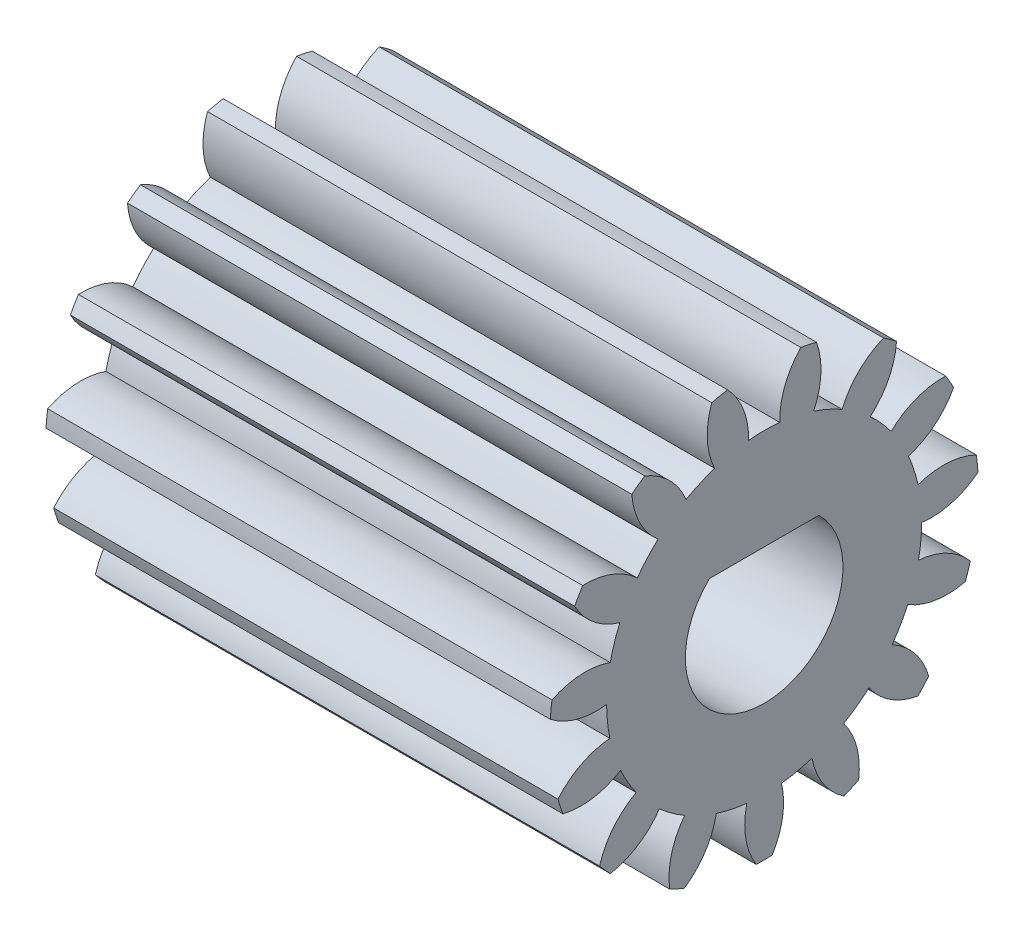
SolidWorks part; units mm, degrees
ref_plane "Plane1" through (0, 0, 0) normal (0, 0, 1) x (1, 0, 0)
ref_plane "Plane2" through (0, 0, 0) normal (0, 1, 0) x (1, 0, 0)
ref_plane "Plane3" through (0, 0, 0) normal (1, 0, 0) x (0, 0, -1)
sketch "HoldingSke" plane through (0, 0, 0) normal (0, 1, 0) x (1, 0, 0)
  line L0 (0, 0) -> (1.2074, -0.3235)
  line L1 (-15, 0) -> (100, 0) construction
  line L2 (0, 0) -> (-2.1039, 2.3779)
  line L3 (0, 0) -> (-11.863, 4.5341)
  line L4 (0, 0) -> (8.3417, 2.2352)
  line L5 (0, 0) -> (-46.8476, -17.4728)
  line L6 (0, 0) -> (-13.2634, -8.9489)
  line L7 (-2.1039, 2.3779) -> (8.6587, 51.2064)
  line L8 (-76.2, 54.61) -> (-75.5, 54.61)
  line L9 (-67.7845, 28.3722) -> (-49.3413, 33.142)
  line L10 (-76.2, 71.12) -> (104.1128, 71.12)
  line L11 (0, 0) -> (-16, 0)
  line L12 (-76.2, 101.6) -> (-76.17, 101.6)
  line L13 (24.9733, 27.94) -> (52.9518, 28.4284)
  line L14 (24.9733, 27.94) -> (24.9743, 27.94)
  line L15 (24.9733, 27.94) -> (100.4006, 29.5858)
  line L16 (-63.627, -0.8) -> (-12.827, -0.8)
  circle A0 centre (0, 0) radius 2
  circle A1 centre (0, 0) radius 4.999
  circle A2 centre (0, 0) radius 37.5
  circle A3 centre (0, 0) radius 2
  dimension "MHD" = 9.998
  dimension "Hub_dia" = 75
  dimension "Bore" = 4
  dimension "MBD" = 4
  dimension "Num_teeth" = 15
  dimension "Pitch" = 1.25
  dimension "Overall_len" = 50
  dimension "Show_teeth" = 15
  dimension "Thickness" = 16
  dimension "OAL" = 50.0006
  dimension "T_dim" = 0.7
  dimension "Ap" = 14.5
  dimension "H" = 19.05
  dimension "Pitch_radius" = 180.3128
  dimension "Width" = 16
  dimension "Backlash" = 0.03
  dimension "Addendum_fac" = 1
  dimension "Dedendum_fac" = 1.25
  dimension "Clearance_fac" = 0.25
  dimension "Dedendum_add" = 0.001
  dimension "Module" = 0.8
sketch "BasProSke" plane through (0, 0, 0) normal (0, 1, 0) x (1, 0, 0)
  line L0 (-10, 0) -> (60, 0) construction
  line L1 (0, 0) -> (0, 6.8)
  line L2 (0, 0) -> (16, 0)
  line L3 (16, 0) -> (16, 6.8)
  line L4 (16, 6.8) -> (0, 6.8)
  dimension "Thickness" = 16
  dimension "Diameter" = 13.6
revolve "Base-Revolve" add sketch "BasProSke" angle 360 about L0
sketch "TooCutSke" plane through (0, 0, 0) normal (1, 0, 0) x (0, 0, -1)
  line L1 (0, 0) -> (0, 107) construction
  line L2 (0, 0) -> (-0.6796, 5.9614) construction
  line L3 (0, 0) -> (-2.4835, 11.6838) construction
  line L4 (-0.6796, 5.9614) -> (-1.2417, 5.8419) construction
  arc A0 (0.4951, 4.9744) -> (-0.4951, 4.9744) centre (0, 0) ccw
  arc A1 (1.1854, 6.7217) -> (-1.1854, 6.7217) centre (0, 0) ccw
  circle A2 centre (0, 0) radius 6 construction
  circle A3 centre (0, 0) radius 5.8089 construction
  arc A4 (-0.4951, 4.9744) -> (-1.1854, 6.7217) centre (-2.8943, 5.0365) ccw
  arc A5 (1.1854, 6.7217) -> (0.4951, 4.9744) centre (2.8943, 5.0365) ccw
  dimension "Root_dia" = 9.998
  dimension "Overcut_dia" = 13.6508
  dimension "Pitch_dia" = 12
  dimension "Base_dia" = 11.6178
  dimension "Flank_rad" = 2.4
  dimension "Half_ang" = 12
  dimension "Half_CT" = 0.5747
extrude "ToothCut" cut sketch "TooCutSke" along normal through all
fillet "Breaks" [suppressed] radius 0.016 tangent propagation no
fillet "RootFillets" [suppressed] radius 0.201
pattern_circular "TeethCuts" count 15 every 24 about axis through (-10, 0, 0) along (1, 0, 0) of "ToothCut", "RootFillets", "Breaks"
sketch "HubNeaOneSke" plane through (0, 0, 0) normal (-1, 0, 0) x (0, 0, 1)
  circle A0 centre (0, 0) radius 4.999
  dimension "Diameter" = 9.998
extrude "HubNearOne" [suppressed] add sketch "HubNeaOneSke" along normal blind 34.0006
sketch "HubNeaBotSke" plane through (0, 0, 0) normal (-1, 0, 0) x (0, 0, 1)
  circle A0 centre (0, 0) radius 4.999
  dimension "Diameter" = 9.998
extrude "HubNearBoth" [suppressed] add sketch "HubNeaBotSke" along normal blind 17.0003
ref_plane "FarPln" through (16, 0, 0) normal (1, 0, 0) x (0, 0, -1)
sketch "HubFarSke" plane through (16, 0, 0) normal (1, 0, 0) x (0, 0, -1)
  circle A0 centre (0, 0) radius 4.999
  dimension "Diameter" = 9.998
extrude "HubFar" [suppressed] add sketch "HubFarSke" along normal blind 17.0003
sketch "BorSke" plane through (0, 0, 0) normal (1, 0, 0) x (0, 0, -1)
  circle A0 centre (0, 0) radius 2
  dimension "Diameter" = 4
extrude "Bore" cut sketch "BorSke" along normal mid plane 100.0011
sketch "KeySke" plane through (0, 0, 0) normal (1, 0, 0) x (0, 0, -1)
  line L0 (-0.8, 0) -> (-0.8, 2.7)
  line L1 (-0.8, 2.7) -> (0.8, 2.7)
  line L2 (0.8, 2.7) -> (0.8, 0)
  line L3 (0, 0) -> (0, 34) construction
  line L4 (-0.8, 0) -> (0.8, 0)
  dimension "Offset" = 2.7
extrude "Keyway" [suppressed] cut sketch "KeySke" along normal mid plane 100.0011
pattern_circular "Keyway2" [suppressed] count 2 every 90 about axis through (-10, 0, 0) along (1, 0, 0) reverse direction yes
sketch "Sketch1" plane through (16, 0, 0) normal (1, 0, 0) x (0, 0, -1)
  line L0 (1.7349, 1.8) -> (-1.7349, 1.8)
  circle A0 centre (0, 0) radius 2.5
  dimension "D1" = 5
  dimension "D2" = 1.8
extrude "Boss-Extrude1" add sketch "Sketch1" against normal through all contours L0 A0 region at (16, 2.0837, 0)
extrude "Cut-Extrude1" cut sketch "Sketch1<3>" against normal through all contours L0 A0 region at (16, -0.1938, 0)
sketch "Sketch1<3>" plane through (16, 0, 0) normal (1, 0, 0) x (0, 0, -1) same geometry as "Sketch1"
equation "' \"Module@HoldingSke\" = 6.35"
equation "' \"Num_teeth@HoldingSke\" = 12"
equation "' \"Ap@HoldingSke\" =  20"
equation "' \"Ap@HoldingSke\" = 20"
equation "' \"Width@HoldingSke\" = 0.5 * 25.4"
equation "' \"Hub_dia@HoldingSke\"= 1 * 25.4"
equation "' \"Hub_dia@HoldingSke\" = 1 * 25.4"
equation "' \"Overall_len@HoldingSke\" = 1.0 * 25.4"
equation "' \"Bore@HoldingSke\" = 0.75 * 25.4"
equation "' \"T_dim@HoldingSke\" = 0.1 * 25.4"
equation "' \"Width@KeySke\" = 0.25 * 25.4"
equation "' \"Show_teeth@HoldingSke\" = 13"
equation "' \"Backlash@HoldingSke\" = 0.009 * 25.4"
equation "' \"Addendum_fac@HoldingSke\" = 1.0"
equation "' \"Dedendum_fac@HoldingSke\" = 1.25"
equation "' \"Dedendum_add@HoldingSke\" = 0.00005 * 25.4"
equation "' \"Clearance_fac@HoldingSke\" = 0.25"
equation "\"Pitch@HoldingSke\" = 1 / \"Module@HoldingSke\""
equation "\"Overcut_dia@TooCutSke\" = (\"Num_teeth@HoldingSke\" + 2 * \"Addendum_fac@HoldingSke\") / \"Pitch@HoldingSke\" + 0.002 * 25.4"
equation "\"Pitch_dia@TooCutSke\" = \"Num_teeth@HoldingSke\" / \"Pitch@HoldingSke\""
equation "\"Base_dia@TooCutSke\" = \"Num_teeth@HoldingSke\" / \"Pitch@HoldingSke\" * cos((\"Ap@HoldingSke\"  * 3.14159265 / 180))"
equation "\"Root_dia@TooCutSke\" = (\"Num_teeth@HoldingSke\" + 2) / \"Pitch@HoldingSke\" - 2 * (\"Addendum_fac@HoldingSke\" + \"Dedendum_fac@HoldingSke\") / \"Pitch@HoldingSke\" - \"Dedendum_add@HoldingSke\" * 2"
equation "\"Half_ang@TooCutSke\" = 180 / \"Num_teeth@HoldingSke\""
equation "\"Half_CT@TooCutSke\" = \"Num_teeth@HoldingSke\" / \"Pitch@HoldingSke\" * sin((3.14159265 / 2 / \"Num_teeth@HoldingSke\")) / 2 - 7 * \"Backlash@HoldingSke\" / 4"
equation "\"Flank_rad@TooCutSke\" = \"Num_teeth@HoldingSke\" / \"Pitch@HoldingSke\" / 5"
equation "\"Radius@RootFillets\" = \"Clearance_fac@HoldingSke\" / \"Pitch@HoldingSke\" + \"Dedendum_add@HoldingSke\""
equation "\"Break_rad@Breaks\" = 0.02 / \"Pitch@HoldingSke\""
equation "\"Thickness@HoldingSke\" = \"Width@HoldingSke\""
equation "\"OAL@HoldingSke\" = \"Thickness@HoldingSke\""
equation "\"MHD@HoldingSke\" = (\"Num_teeth@HoldingSke\" + 2) / \"Pitch@HoldingSke\" - 2 * (\"Addendum_fac@HoldingSke\" + \"Dedendum_fac@HoldingSke\")  / \"Pitch@HoldingSke\" - \"Dedendum_add@HoldingSke\" * 2"
equation "\"MBD@HoldingSke\" = (\"Num_teeth@HoldingSke\" + 2) / \"Pitch@HoldingSke\" - 2 * (\"Addendum_fac@HoldingSke\" + \"Dedendum_fac@HoldingSke\")  / \"Pitch@HoldingSke\" - \"Dedendum_add@HoldingSke\" * 2 - 0.002 * 25.4"
equation "\"MHD@HoldingSke\" = ((sgn( \"MHD@HoldingSke\" - \"Hub_dia@HoldingSke\" )-1)*( \"MHD@HoldingSke\" - \"Hub_dia@HoldingSke\" ))/-2+ \"Hub_dia@HoldingSke\""
equation "\"MBD@HoldingSke\" = ((sgn( \"MBD@HoldingSke\" - \"Bore@HoldingSke\" )-1)*( \"MBD@HoldingSke\" - \"Bore@HoldingSke\" ))/-2+ \"Bore@HoldingSke\""
equation "\"OAL@HoldingSke\" = ((sgn( \"OAL@HoldingSke\" - \"Overall_len@HoldingSke\" )+1)*( \"OAL@HoldingSke\" - \"Overall_len@HoldingSke\" ))/2 + \"Overall_len@HoldingSke\" + 0.000002 * 25.4"
equation "\"Num_teeth@TeethCuts\" = int( \"Show_teeth@HoldingSke\" ) + 1"
equation "\"Num_teeth@TeethCuts\" = ((sgn( \"Num_teeth@TeethCuts\" - \"Num_teeth@HoldingSke\" )-1)*( \"Num_teeth@TeethCuts\" - \"Num_teeth@HoldingSke\" ))/-2+ \"Num_teeth@HoldingSke\""
equation "\"Num_teeth@TeethCuts\" = ((sgn( \"Num_teeth@TeethCuts\" - 2.0)+1)*( \"Num_teeth@TeethCuts\" - 2.0))/2 +2.0"
equation "\"Angle@TeethCuts\" = 360.0 / \"Num_teeth@HoldingSke\""
equation "\"Diameter@BasProSke\" = (\"Num_teeth@HoldingSke\" + 2 * \"Addendum_fac@HoldingSke\") / \"Pitch@HoldingSke\""
equation "\"Thickness@BasProSke\"  = \"Thickness@HoldingSke\""
equation "' \"Fillet_rad@BasProSke\" =  \"Thickness@HoldingSke\" * 0.05"
equation "' \"Fillet_rad@BasProSke\" = \"Thickness@HoldingSke\" * 0.05"
equation "\"MHD@HoldingSke\" = ((sgn( \"MHD@HoldingSke\" - \"Root_dia@TooCutSke\" )-1)*( \"MHD@HoldingSke\" - \"Root_dia@TooCutSke\" ))/-2+ \"Root_dia@TooCutSke\""
equation "\"Diameter@HubNeaOneSke\" = \"MHD@HoldingSke\""
equation "\"Length@HubNearOne\" = \"OAL@HoldingSke\" - \"Thickness@BasProSke\""
equation "\"Diameter@HubNeaBotSke\" = \"MHD@HoldingSke\""
equation "\"Length@HubNearBoth\" = ( \"OAL@HoldingSke\" - \"Thickness@BasProSke\" ) / 2.0"
equation "\"Thickness@FarPln\" = \"Thickness@BasProSke\""
equation "\"Diameter@HubFarSke\" = \"MHD@HoldingSke\""
equation "\"Length@HubFar\" = ( \"OAL@HoldingSke\" - \"Thickness@BasProSke\" ) / 2.0"
equation "\"Diameter@BorSke\" = \"MBD@HoldingSke\""
equation "\"D1@Bore\" = \"OAL@HoldingSke\" * 2.0"
equation "\"D1@Keyway\" = \"OAL@HoldingSke\" * 2.0"
equation "\"Offset@KeySke\" = \"T_dim@HoldingSke\" + \"MBD@HoldingSke\" / 2.0"
equation "\"D2@Sketch1\"=4.3-2.5"
